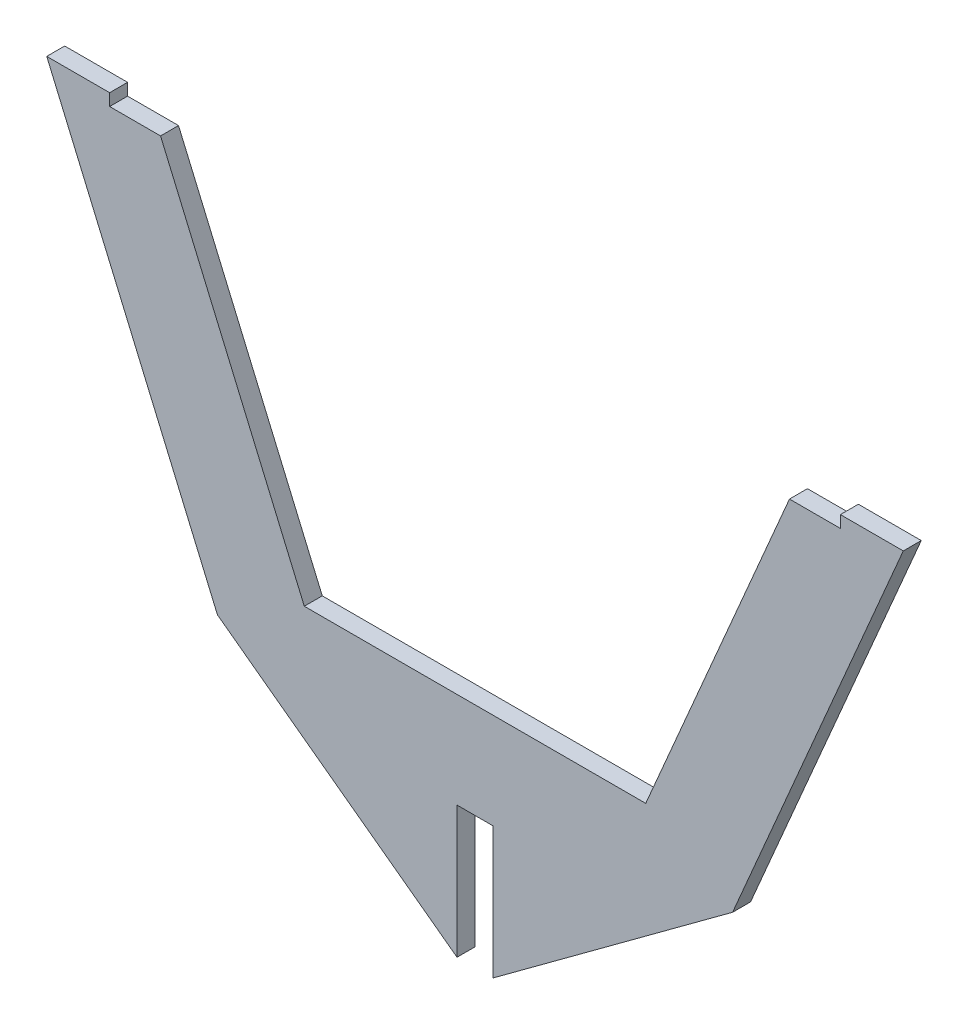
SolidWorks part; units mm, degrees
ref_plane "Plan de face" through (0, 0, 0) normal (0, 0, 1) x (1, 0, 0)
ref_plane "Plan de dessus" through (0, 0, 0) normal (0, 1, 0) x (1, 0, 0)
ref_plane "Plan de droite" through (0, 0, 0) normal (1, 0, 0) x (0, 0, -1)
sketch "Esquisse1" plane through (0, 0, 0) normal (0, 1, 0) x (1, 0, 0)
  point P0 (0, 27.1237)
sketch "Esquisse3" plane through (0, 0, 0) normal (0, 0, 1) x (1, 0, 0)
  line L43 (-10.1935, 41.5753) -> (0.3065, 41.5753)
  line L44 (0.3065, 41.5753) -> (0.3065, 39.5753)
  line L45 (0.3065, 39.5753) -> (8.8065, 39.5753)
  line L46 (8.8065, 39.5753) -> (32.8065, -16.4247)
  line L47 (32.8065, -16.4247) -> (52.2492, -16.4247)
  line L48 (-10.1935, 41.5753) -> (18.3065, -24.9247)
  line L49 (18.3065, -24.9247) -> (25.1363, -29.9617)
  line L50 (25.1363, -29.9617) -> (58.3065, -54.4247)
  line L51 (58.3065, -54.4247) -> (58.3065, -32.4247)
  line L52 (64.3065, -32.4247) -> (58.3065, -32.4247)
  line L53 (70.3637, -16.4247) -> (52.2492, -16.4247)
  line L54 (61.3065, -32.4247) -> (61.3065, -16.4247) construction
  line L55 (64.3065, -54.4247) -> (64.3065, -32.4247)
  line L56 (104.3065, -24.9247) -> (97.4767, -29.9617)
  line L57 (132.8065, 41.5753) -> (104.3065, -24.9247)
  line L58 (132.8065, 41.5753) -> (122.3065, 41.5753)
  line L59 (122.3065, 41.5753) -> (122.3065, 39.5753)
  line L60 (122.3065, 39.5753) -> (113.8065, 39.5753)
  line L61 (113.8065, 39.5753) -> (89.8065, -16.4247)
  line L62 (89.8065, -16.4247) -> (70.3637, -16.4247)
  line L63 (97.4767, -29.9617) -> (64.3065, -54.4247)
  dimension "D1" = 105
  dimension "D2" = 143
  dimension "D3" = 122
  dimension "D4" = 57
  dimension "D5" = 86
  dimension "D6" = 6
  dimension "D7" = 2
  dimension "D8" = 96
  dimension "D9" = 38
  dimension "D10" = 38
  dimension "D11" = 22
extrude "Boss.-Extru.3" add sketch "Esquisse3" along normal blind 3
